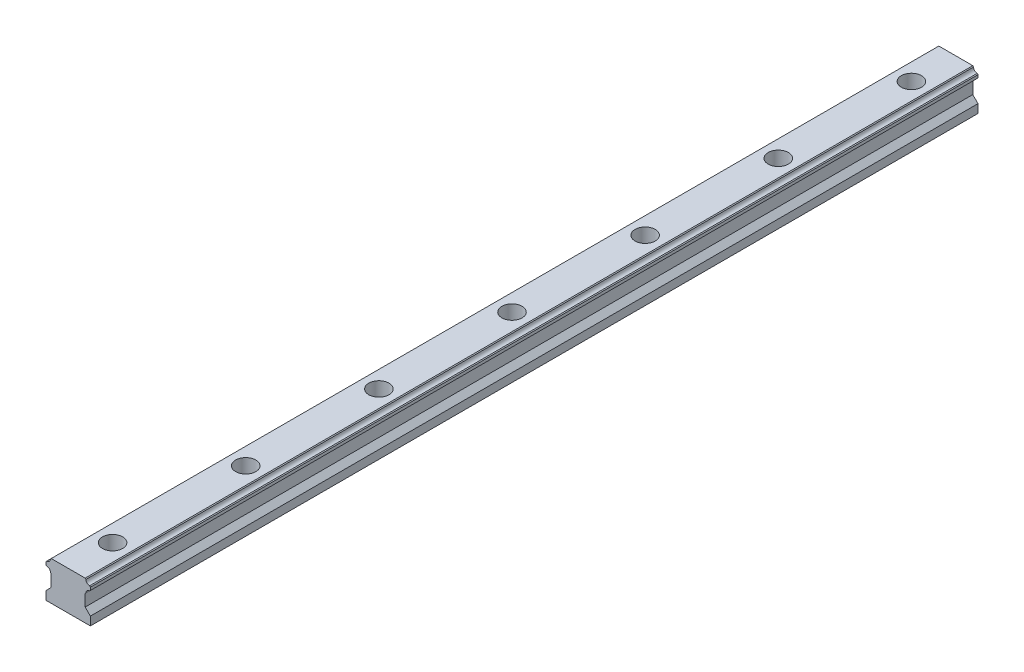
SolidWorks part; units mm, degrees
material "Plain Carbon Steel"
ref_plane "Front Plane" through (0, 0, 0) normal (0, 0, 1) x (1, 0, 0)
ref_plane "Top Plane" through (0, 0, 0) normal (0, 1, 0) x (1, 0, 0)
ref_plane "Right Plane" through (0, 0, 0) normal (1, 0, 0) x (0, 0, -1)
sketch "Sketch1" plane through (0, 0, 0) normal (0, 0, 1) x (1, 0, 0)
  line L0 (0, 13.3681) -> (0, -3.2505) construction
  line L1 (-6.5, -4.15) -> (-6.5, -7.15)
  line L3 (-6.5, -7.15) -> (-10, -10.65)
  line L4 (-10, -10.65) -> (-10, -14.5)
  line L5 (-8.0036, 2.6464) -> (-9.6464, 2.6464) construction
  line L6 (-10, -14.5) -> (0, -14.5)
  line L7 (-6.5, -4.15) -> (-8.0036, -2.6464)
  line L8 (-10, -0.65) -> (-10, 0.65)
  line L9 (-10, 0.65) -> (-9.6464, 1.0036)
  line L10 (-7.65, 3) -> (0, 3)
  line L11 (-10, -0.65) -> (-10, -10.65) construction
  line L12 (-10, 0) -> (0, 0) construction
  line L13 (-8.0036, 2.6464) -> (-7.65, 3)
  line L14 (-9.6464, -1.0036) -> (-10, -0.65)
  line L15 (0, 3) -> (0, -14.5)
  line L16 (-9.6464, 2.6464) -> (-9.6464, 1.0036) construction
  arc A0 (-9.6464, 1.0036) -> (-8.0036, 2.6464) centre (-9.6464, 2.6464) ccw
  arc A1 (-9.6464, -1.0036) -> (-8.0036, -2.6464) centre (-9.6464, -2.6464) cw
  dimension "D5" = 0.5
  dimension "D1" = 14.5
  dimension "D2" = 3
  dimension "D3" = 7.65
  dimension "D4" = 10
  dimension "D6" = 1.3
  dimension "D7" = 17.5
  dimension "D8" = 6.5
  dimension "D9" = 45
extrude "Boss-Extrude1" add sketch "Sketch1" along normal blind 200
mirror "Mirror1" about plane through (0, 3, 200) normal (-1, 0, 0) of "Boss-Extrude1"
sketch "Sketch2" plane through (0, 3, 0) normal (0, 1, 0) x (1, 0, 0)
  line L0 (0, 130.187) -> (0, 31.9327) construction
  line L1 (7.65, 0) -> (-7.65, 0) construction
  circle A0 centre (0, -30) radius 3
  dimension "D1" = 6
  dimension "D2" = 30
extrude "Cut-Extrude1" cut sketch "Sketch2" against normal through all
sketch "Sketch3" plane through (0, 3, 0) normal (0, 1, 0) x (1, 0, 0)
  circle A0 centre (0, -30) radius 4.75
  dimension "D1" = 9.5
extrude "Cut-Extrude2" cut sketch "Sketch3" against normal blind 8.5
pattern_linear "LPattern1" count 100 spacing 60 along (0, 0, 1) of "Cut-Extrude1", "Cut-Extrude2"
mirror "Mirror2" about plane through (-9.6464, -2.6464, 0) normal (0, 0, -1) of bodies 106
sketch "Sketch4" plane through (0, 3, 0) normal (0, 1, 0) x (1, 0, 0)
  line L1 (-7.65, 200) -> (7.65, 200)
  line L2 (-7.65, 200) -> (-7.65, -200)
  line L3 (-7.65, -200) -> (7.65, -200)
  line L4 (7.65, 200) -> (7.65, -200)
extrude "Boss-Extrude2" add sketch "Sketch4" against normal up to surface (17.5 mm away) up to face at (0, -14.5, 153)
sketch "Sketch5" plane through (0, 3, 0) normal (0, 1, 0) x (1, 0, 0)
  line L0 (0, 180) -> (0, 120) construction
  line L1 (0, 120) -> (0, 60) construction
  line L2 (0, 60) -> (0, 0) construction
  line L3 (0, 0) -> (0, -60) construction
  line L4 (0, -60) -> (0, -120) construction
  line L5 (0, -120) -> (0, -180) construction
  line L6 (0, 180) -> (0, 200) construction
  line L7 (0, -180) -> (0, -200) construction
  line L8 (7.65, 200) -> (-7.65, 200) construction
  line L9 (7.65, -200) -> (-7.65, -200) construction
  circle A0 centre (0, 180) radius 2.9
  circle A1 centre (0, 120) radius 2.9
  circle A2 centre (0, 60) radius 2.9
  circle A3 centre (0, 0) radius 2.9
  circle A4 centre (0, -60) radius 2.9
  circle A5 centre (0, -120) radius 2.9
  circle A6 centre (0, -180) radius 2.9
  point P16 (0, 0)
  point P17 (0, 200)
  point P20 (0, -200)
  dimension "D1" = 5.8
  dimension "D2" = 20
extrude "Cut-Extrude3" cut sketch "Sketch5" against normal through all
sketch "Sketch6" plane through (0, 3, 0) normal (0, 1, 0) x (1, 0, 0)
  circle A0 centre (0, 180) radius 4.55
  circle A1 centre (0, 120) radius 4.55
  circle A2 centre (0, 60) radius 4.55
  circle A3 centre (0, 0) radius 4.55
  circle A4 centre (0, -60) radius 4.55
  circle A5 centre (0, -120) radius 4.55
  circle A6 centre (0, -180) radius 4.55
  dimension "D1" = 9.1
extrude "Cut-Extrude4" cut sketch "Sketch6" against normal blind 8.9
equation "\"length\"= 400mm"
equation "\"D1@Boss-Extrude1\" = \"length\" /2"
equation "\"M5_tap\"=4.2mm\t\t\t\t\t\t\t' Below you can do mesurements as follows: cm, mm, ft, in, m, "
equation "\"M5_clearence\"=5.5mm"
equation "\"M6_tap\"=5mm"
equation "\"M6_clearence\"=6.6mm"
equation "\"work_area_width\"=1100mm"
equation "\"work_area_depth\"=900mm"
